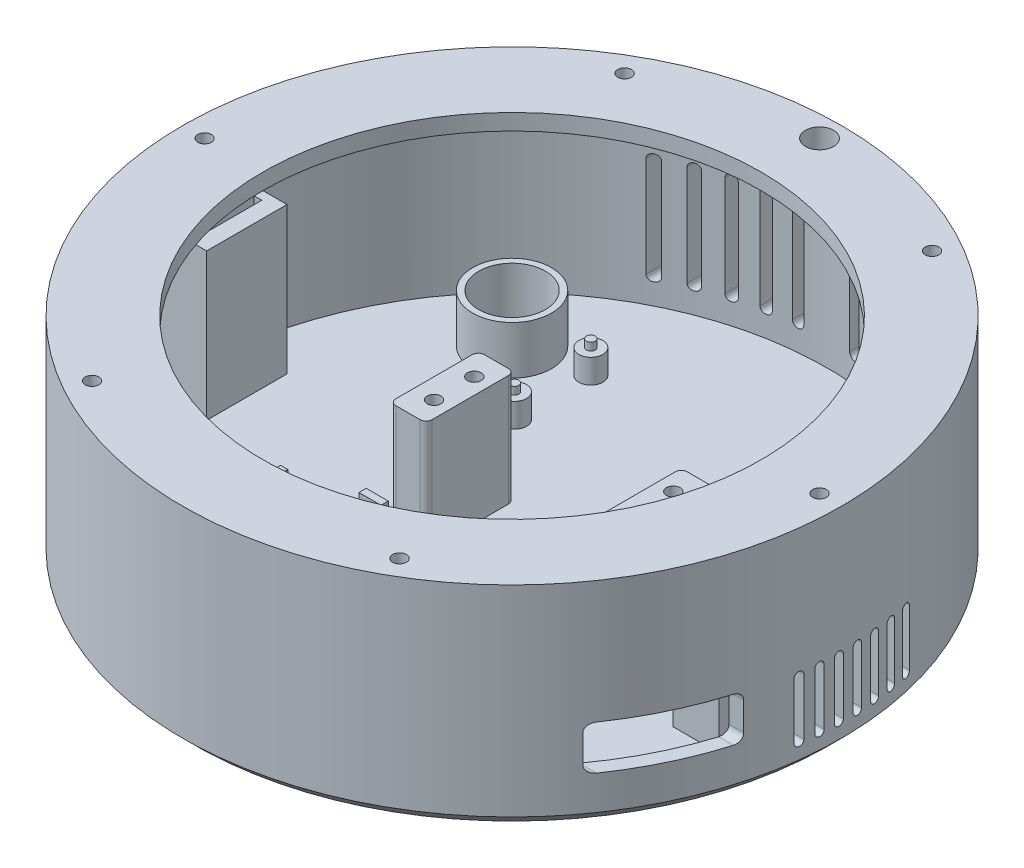
SolidWorks part; units mm, degrees
ref_plane "Front Plane" through (0, 0, 0) normal (0, 0, 1) x (1, 0, 0)
ref_plane "Top Plane" through (0, 0, 0) normal (0, 1, 0) x (1, 0, 0)
ref_plane "Right Plane" through (0, 0, 0) normal (1, 0, 0) x (0, 0, -1)
sketch "Sketch1" plane through (0, 0, 0) normal (0, 0, 1) x (1, 0, 0)
  line L0 (0, -5) -> (0, 80) construction
  line L1 (0, 0) -> (79, 0)
  line L2 (79, 0) -> (82, 3)
  line L3 (82, 3) -> (82, 53)
  line L4 (82, 53) -> (62, 53)
  line L5 (62, 53) -> (62, 49)
  line L6 (62, 49) -> (70.5, 49)
  line L7 (70.5, 49) -> (70.5, 47)
  line L8 (70.5, 47) -> (78.5, 47)
  line L9 (78.5, 47) -> (78.5, 2.5)
  line L10 (78.5, 2.5) -> (0, 2.5)
  line L11 (0, 2.5) -> (0, 0)
revolve "Shell + slew ring" add sketch "Sketch1" angle 360 about L0
sketch "Sketch2" plane through (0, 0, 0) normal (0, 1, 0) x (1, 0, 0)
  line L0 (-17.9, 11) -> (-11.9, 11)
  line L1 (-10.4, 9.5) -> (-10.4, -9.5)
  line L2 (-11.9, -11) -> (-17.9, -11)
  line L3 (-19.4, -9.5) -> (-19.4, 9.5)
  line L4 (32.6, 11) -> (38.6, 11)
  line L5 (40.1, 9.5) -> (40.1, -9.5)
  line L6 (38.6, -11) -> (32.6, -11)
  line L7 (31.1, -9.5) -> (31.1, 9.5)
  arc A0 (-19.4, 9.5) -> (-17.9, 11) centre (-17.9, 9.5) cw
  arc A1 (-11.9, 11) -> (-10.4, 9.5) centre (-11.9, 9.5) cw
  arc A2 (-10.4, -9.5) -> (-11.9, -11) centre (-11.9, -9.5) cw
  arc A3 (-17.9, -11) -> (-19.4, -9.5) centre (-17.9, -9.5) cw
  arc A4 (31.1, 9.5) -> (32.6, 11) centre (32.6, 9.5) cw
  arc A5 (38.6, 11) -> (40.1, 9.5) centre (38.6, 9.5) cw
  arc A6 (40.1, -9.5) -> (38.6, -11) centre (38.6, -9.5) cw
  arc A7 (32.6, -11) -> (31.1, -9.5) centre (32.6, -9.5) cw
extrude "Pan servo pillars" add sketch "Sketch2" along normal blind 27.9 from offset 2.3
sketch "Sketch3" plane through (0, 0, 0) normal (0, 1, 0) x (1, 0, 0)
  circle A0 centre (-14.4, 5) radius 1.7
  circle A1 centre (-14.4, -5) radius 1.7
  circle A2 centre (35.1, 5) radius 1.7
  circle A3 centre (35.1, -5) radius 1.7
extrude "Pillar bolt holes" cut sketch "Sketch3" along normal blind 13.2 from offset 17.2
sketch "Sketch4" plane through (0, 0, 0) normal (0, 1, 0) x (1, 0, 0)
  line L0 (-16.1032, 7.95) -> (-12.6968, 7.95)
  line L1 (-12.6968, 7.95) -> (-10.9936, 5)
  line L2 (-10.9936, 5) -> (-12.6968, 2.05)
  line L3 (-12.6968, 2.05) -> (-16.1032, 2.05)
  line L4 (-16.1032, 2.05) -> (-19.9, 2.05)
  line L5 (-19.9, 2.05) -> (-19.9, 7.95)
  line L6 (-19.9, 7.95) -> (-16.1032, 7.95)
  line L7 (-16.1032, -2.05) -> (-12.6968, -2.05)
  line L8 (-12.6968, -2.05) -> (-10.9936, -5)
  line L9 (-10.9936, -5) -> (-12.6968, -7.95)
  line L10 (-12.6968, -7.95) -> (-16.1032, -7.95)
  line L11 (-16.1032, -7.95) -> (-19.9, -7.95)
  line L12 (-19.9, -7.95) -> (-19.9, -2.05)
  line L13 (-19.9, -2.05) -> (-16.1032, -2.05)
  line L14 (36.8032, 2.05) -> (33.3968, 2.05)
  line L15 (33.3968, 2.05) -> (31.6936, 5)
  line L16 (31.6936, 5) -> (33.3968, 7.95)
  line L17 (33.3968, 7.95) -> (36.8032, 7.95)
  line L18 (36.8032, 7.95) -> (40.6, 7.95)
  line L19 (40.6, 7.95) -> (40.6, 2.05)
  line L20 (40.6, 2.05) -> (36.8032, 2.05)
  line L21 (36.8032, -7.95) -> (33.3968, -7.95)
  line L22 (33.3968, -7.95) -> (31.6936, -5)
  line L23 (31.6936, -5) -> (33.3968, -2.05)
  line L24 (33.3968, -2.05) -> (36.8032, -2.05)
  line L25 (36.8032, -2.05) -> (40.6, -2.05)
  line L26 (40.6, -2.05) -> (40.6, -7.95)
  line L27 (40.6, -7.95) -> (36.8032, -7.95)
extrude "Pillar nut slots" cut sketch "Sketch4" along normal blind 2.7 from offset 21.5
sketch "Sketch5" plane through (0, 0, 0) normal (0, 1, 0) x (1, 0, 0)
  line L0 (30.5, 4.5) -> (40.7, 4.5)
  line L1 (40.7, 4.5) -> (40.7, -4.5)
  line L2 (40.7, -4.5) -> (30.5, -4.5)
  line L3 (30.5, -4.5) -> (30.5, 4.5)
extrude "Servo lead notch" cut sketch "Sketch5" along normal blind 10.7 from offset 2.3
sketch "Sketch6" plane through (0, 0, 0) normal (0, 1, 0) x (1, 0, 0)
  circle A0 centre (-27.9, 47.5) radius 3
  circle A1 centre (-27.9, 28.5) radius 3
  circle A2 centre (27.9, 47.5) radius 3
  circle A3 centre (27.9, 28.5) radius 3
extrude "PCA9685 posts" add sketch "Sketch6" along normal blind 6.2 from offset 2.3
sketch "Sketch7" plane through (0, 0, 0) normal (0, 1, 0) x (1, 0, 0)
  circle A0 centre (-27.9, 47.5) radius 1.1
  circle A1 centre (-27.9, 28.5) radius 1.1
  circle A2 centre (27.9, 47.5) radius 1.1
  circle A3 centre (27.9, 28.5) radius 1.1
extrude "PCA9685 locating pins" add sketch "Sketch7" along normal blind 2.1 from offset 8.3
sketch "Sketch8" plane through (0, 0, 0) normal (0, 1, 0) x (1, 0, 0)
  circle A0 centre (-16.5, -26.5) radius 2.7
  circle A1 centre (-16.5, -43.5) radius 2.7
  circle A2 centre (39.5, -26.5) radius 2.7
  circle A3 centre (39.5, -43.5) radius 2.7
extrude "ESP32 posts" add sketch "Sketch8" along normal blind 10.2 from offset 2.3
sketch "Sketch9" plane through (0, 0, 0) normal (0, 1, 0) x (1, 0, 0)
  line L0 (-13, -19.6) -> (-18.5, -19.6)
  line L1 (-18.5, -19.6) -> (-18.5, -17.8)
  line L2 (-18.5, -17.8) -> (-13, -17.8)
  line L3 (-13, -17.8) -> (-13, -19.6)
  line L4 (-13, -50.4) -> (-18.5, -50.4)
  line L5 (-18.5, -50.4) -> (-18.5, -52.2)
  line L6 (-18.5, -52.2) -> (-13, -52.2)
  line L7 (-13, -52.2) -> (-13, -50.4)
  line L8 (39, -19.6) -> (44.5, -19.6)
  line L9 (44.5, -19.6) -> (44.5, -17.8)
  line L10 (44.5, -17.8) -> (39, -17.8)
  line L11 (39, -17.8) -> (39, -19.6)
  line L12 (39, -50.4) -> (44.5, -50.4)
  line L13 (44.5, -50.4) -> (44.5, -52.2)
  line L14 (44.5, -52.2) -> (39, -52.2)
  line L15 (39, -52.2) -> (39, -50.4)
extrude "ESP32 fences" add sketch "Sketch9" along normal blind 13.2 from offset 2.3
sketch "Sketch10" plane through (0, 0, 0) normal (0, 1, 0) x (1, 0, 0)
  circle A0 centre (-54.5, -27.5) radius 2.7
  circle A1 centre (-54.5, -36) radius 2.7
  circle A2 centre (-39.5, -27.5) radius 2.7
  circle A3 centre (-39.5, -36) radius 2.7
extrude "Amp posts" add sketch "Sketch10" along normal blind 7.7 from offset 2.3
sketch "Sketch11" plane through (0, 0, 0) normal (0, 1, 0) x (1, 0, 0)
  line L0 (-57.4, -26) -> (-59.2, -26)
  line L1 (-59.2, -26) -> (-59.2, -21)
  line L2 (-59.2, -21) -> (-57.4, -21)
  line L3 (-57.4, -21) -> (-57.4, -26)
  line L4 (-57.4, -34) -> (-59.2, -34)
  line L5 (-59.2, -34) -> (-59.2, -39)
  line L6 (-59.2, -39) -> (-57.4, -39)
  line L7 (-57.4, -39) -> (-57.4, -34)
  line L8 (-36.6, -26) -> (-34.8, -26)
  line L9 (-34.8, -26) -> (-34.8, -21)
  line L10 (-34.8, -21) -> (-36.6, -21)
  line L11 (-36.6, -21) -> (-36.6, -26)
  line L12 (-36.6, -34) -> (-34.8, -34)
  line L13 (-34.8, -34) -> (-34.8, -39)
  line L14 (-34.8, -39) -> (-36.6, -39)
  line L15 (-36.6, -39) -> (-36.6, -34)
extrude "Amp fences" add sketch "Sketch11" along normal blind 10.7 from offset 2.3
sketch "Sketch12" plane through (0, 0, 0) normal (0, 1, 0) x (1, 0, 0)
  line L0 (58, -15) -> (69.5, -15)
  line L1 (69.5, -15) -> (69.5, -18)
  line L2 (69.5, -18) -> (58, -18)
  line L3 (58, -18) -> (58, -15)
  line L4 (58, 26) -> (69.5, 26)
  line L5 (69.5, 26) -> (69.5, 23)
  line L6 (69.5, 23) -> (58, 23)
  line L7 (58, 23) -> (58, 26)
extrude "Speaker rails" add sketch "Sketch12" along normal blind 24.2 from offset 2.3
sketch "Sketch13" plane through (0, 0, 0) normal (0, 1, 0) x (1, 0, 0)
  line L0 (60.7, -14.9) -> (66.8, -14.9)
  line L1 (66.8, -14.9) -> (66.8, -16.4)
  line L2 (66.8, -16.4) -> (60.7, -16.4)
  line L3 (60.7, -16.4) -> (60.7, -14.9)
  line L4 (60.7, 24.4) -> (66.8, 24.4)
  line L5 (66.8, 24.4) -> (66.8, 22.9)
  line L6 (66.8, 22.9) -> (60.7, 22.9)
  line L7 (60.7, 22.9) -> (60.7, 24.4)
extrude "Speaker grooves" cut sketch "Sketch13" along normal blind 23.2 from offset 3.5
sketch "Sketch14" plane through (0, 0, 0) normal (0, 1, 0) x (1, 0, 0)
  line L0 (-79.5, 10) -> (-66, 10)
  line L1 (-66, 10) -> (-66, -10)
  line L2 (-66, -10) -> (-79.5, -10)
  line L3 (-79.5, -10) -> (-79.5, 10)
extrude "Mic block" add sketch "Sketch14" along normal blind 36.7 from offset 2.3
sketch "Sketch15" plane through (0, 0, 0) normal (0, 1, 0) x (1, 0, 0)
  line L0 (-71.95, 7.8) -> (-70.05, 7.8)
  line L1 (-70.05, 7.8) -> (-70.05, -7.8)
  line L2 (-70.05, -7.8) -> (-71.95, -7.8)
  line L3 (-71.95, -7.8) -> (-71.95, 7.8)
extrude "Mic slot" cut sketch "Sketch15" along normal blind 17.2 from offset 22
sketch "Sketch16" plane through (0, 0, 0) normal (1, 0, 0) x (0, 0, -1)
  circle A0 centre (0, 30) radius 1.25
extrude "Mic port" cut sketch "Sketch16" along normal blind 19 from offset 90 offset against normal yes
sketch "Sketch17" plane through (0, 0, 0) normal (0, 1, 0) x (1, 0, 0)
  circle A0 centre (-44, 44) radius 9.8
  circle A1 centre (-44, 44) radius 8.3
extrude "Cap clip" add sketch "Sketch17" along normal blind 12.2 from offset 2.3
sketch "Sketch18" plane through (0, 0, 0) normal (1, 0, 0) x (0, 0, -1)
  line L0 (16.9, 7) -> (16.9, 21)
  line L1 (19.1, 21) -> (19.1, 7)
  line L2 (12.2333, 7) -> (12.2333, 21)
  line L3 (14.4333, 21) -> (14.4333, 7)
  line L4 (7.5667, 7) -> (7.5667, 21)
  line L5 (9.7667, 21) -> (9.7667, 7)
  line L6 (2.9, 7) -> (2.9, 21)
  line L7 (5.1, 21) -> (5.1, 7)
  line L8 (-1.7667, 7) -> (-1.7667, 21)
  line L9 (0.4333, 21) -> (0.4333, 7)
  line L10 (-6.4333, 7) -> (-6.4333, 21)
  line L11 (-4.2333, 21) -> (-4.2333, 7)
  line L12 (-11.1, 7) -> (-11.1, 21)
  line L13 (-8.9, 21) -> (-8.9, 7)
  arc A0 (16.9, 21) -> (19.1, 21) centre (18, 21) cw
  arc A1 (19.1, 7) -> (16.9, 7) centre (18, 7) cw
  arc A2 (12.2333, 21) -> (14.4333, 21) centre (13.3333, 21) cw
  arc A3 (14.4333, 7) -> (12.2333, 7) centre (13.3333, 7) cw
  arc A4 (7.5667, 21) -> (9.7667, 21) centre (8.6667, 21) cw
  arc A5 (9.7667, 7) -> (7.5667, 7) centre (8.6667, 7) cw
  arc A6 (2.9, 21) -> (5.1, 21) centre (4, 21) cw
  arc A7 (5.1, 7) -> (2.9, 7) centre (4, 7) cw
  arc A8 (-1.7667, 21) -> (0.4333, 21) centre (-0.6667, 21) cw
  arc A9 (0.4333, 7) -> (-1.7667, 7) centre (-0.6667, 7) cw
  arc A10 (-6.4333, 21) -> (-4.2333, 21) centre (-5.3333, 21) cw
  arc A11 (-4.2333, 7) -> (-6.4333, 7) centre (-5.3333, 7) cw
  arc A12 (-11.1, 21) -> (-8.9, 21) centre (-10, 21) cw
  arc A13 (-8.9, 7) -> (-11.1, 7) centre (-10, 7) cw
extrude "Speaker grille" cut sketch "Sketch18" along normal blind 24 from offset 66
sketch "Sketch19" plane through (0, 0, 0) normal (1, 0, 0) x (0, 0, -1)
  line L0 (-21.5, 13.5) -> (-21.5, 20.5)
  line L1 (-23.5, 22.5) -> (-46.5, 22.5)
  line L2 (-48.5, 20.5) -> (-48.5, 13.5)
  line L3 (-46.5, 11.5) -> (-23.5, 11.5)
  arc A0 (-23.5, 11.5) -> (-21.5, 13.5) centre (-23.5, 13.5) ccw
  arc A1 (-21.5, 20.5) -> (-23.5, 22.5) centre (-23.5, 20.5) ccw
  arc A2 (-46.5, 22.5) -> (-48.5, 20.5) centre (-46.5, 20.5) ccw
  arc A3 (-48.5, 13.5) -> (-46.5, 11.5) centre (-46.5, 13.5) ccw
extrude "USB window" cut sketch "Sketch19" along normal blind 44 from offset 46
sketch "Sketch20" plane through (0, 0, 0) normal (0, 0, 1) x (1, 0, 0)
  line L0 (-36.3, 9) -> (-36.3, 34)
  line L1 (-33.7, 34) -> (-33.7, 9)
  line L2 (-29.3, 9) -> (-29.3, 34)
  line L3 (-26.7, 34) -> (-26.7, 9)
  line L4 (-22.3, 9) -> (-22.3, 34)
  line L5 (-19.7, 34) -> (-19.7, 9)
  line L6 (-15.3, 9) -> (-15.3, 34)
  line L7 (-12.7, 34) -> (-12.7, 9)
  line L8 (-8.3, 9) -> (-8.3, 34)
  line L9 (-5.7, 34) -> (-5.7, 9)
  line L10 (5.7, 9) -> (5.7, 34)
  line L11 (8.3, 34) -> (8.3, 9)
  line L12 (12.7, 9) -> (12.7, 34)
  line L13 (15.3, 34) -> (15.3, 9)
  line L14 (19.7, 9) -> (19.7, 34)
  line L15 (22.3, 34) -> (22.3, 9)
  line L16 (26.7, 9) -> (26.7, 34)
  line L17 (29.3, 34) -> (29.3, 9)
  line L18 (33.7, 9) -> (33.7, 34)
  line L19 (36.3, 34) -> (36.3, 9)
  arc A0 (-36.3, 34) -> (-33.7, 34) centre (-35, 34) cw
  arc A1 (-33.7, 9) -> (-36.3, 9) centre (-35, 9) cw
  arc A2 (-29.3, 34) -> (-26.7, 34) centre (-28, 34) cw
  arc A3 (-26.7, 9) -> (-29.3, 9) centre (-28, 9) cw
  arc A4 (-22.3, 34) -> (-19.7, 34) centre (-21, 34) cw
  arc A5 (-19.7, 9) -> (-22.3, 9) centre (-21, 9) cw
  arc A6 (-15.3, 34) -> (-12.7, 34) centre (-14, 34) cw
  arc A7 (-12.7, 9) -> (-15.3, 9) centre (-14, 9) cw
  arc A8 (-8.3, 34) -> (-5.7, 34) centre (-7, 34) cw
  arc A9 (-5.7, 9) -> (-8.3, 9) centre (-7, 9) cw
  arc A10 (5.7, 34) -> (8.3, 34) centre (7, 34) cw
  arc A11 (8.3, 9) -> (5.7, 9) centre (7, 9) cw
  arc A12 (12.7, 34) -> (15.3, 34) centre (14, 34) cw
  arc A13 (15.3, 9) -> (12.7, 9) centre (14, 9) cw
  arc A14 (19.7, 34) -> (22.3, 34) centre (21, 34) cw
  arc A15 (22.3, 9) -> (19.7, 9) centre (21, 9) cw
  arc A16 (26.7, 34) -> (29.3, 34) centre (28, 34) cw
  arc A17 (29.3, 9) -> (26.7, 9) centre (28, 9) cw
  arc A18 (33.7, 34) -> (36.3, 34) centre (35, 34) cw
  arc A19 (36.3, 9) -> (33.7, 9) centre (35, 9) cw
extrude "Back vents" cut sketch "Sketch20" along normal blind 30 from offset 90 offset against normal yes
sketch "Sketch21" plane through (0, 0, 0) normal (0, 1, 0) x (1, 0, 0)
  circle A0 centre (76.5, 0) radius 1.7
  circle A1 centre (38.25, -66.2509) radius 1.7
  circle A2 centre (-38.25, -66.2509) radius 1.7
  circle A3 centre (-76.5, 0) radius 1.7
  circle A4 centre (-38.25, 66.2509) radius 1.7
  circle A5 centre (38.25, 66.2509) radius 1.7
extrude "Ring bolt holes" cut sketch "Sketch21" along normal blind 6.4 from offset 46.8
sketch "Sketch22" plane through (0, 0, 0) normal (0, 1, 0) x (1, 0, 0)
  line L0 (79.35, -1.6454) -> (76.5, -3.2909)
  line L1 (76.5, -3.2909) -> (73.65, -1.6454)
  line L2 (73.65, -1.6454) -> (73.65, 1.6454)
  line L3 (73.65, 1.6454) -> (76.5, 3.2909)
  line L4 (76.5, 3.2909) -> (79.35, 1.6454)
  line L5 (79.35, 1.6454) -> (79.35, -1.6454)
  line L6 (38.25, -69.5418) -> (35.4, -67.8964)
  line L7 (35.4, -67.8964) -> (35.4, -64.6055)
  line L8 (35.4, -64.6055) -> (38.25, -62.96)
  line L9 (38.25, -62.96) -> (41.1, -64.6055)
  line L10 (41.1, -64.6055) -> (41.1, -67.8964)
  line L11 (41.1, -67.8964) -> (38.25, -69.5418)
  line L12 (-41.1, -67.8964) -> (-41.1, -64.6055)
  line L13 (-41.1, -64.6055) -> (-38.25, -62.96)
  line L14 (-38.25, -62.96) -> (-35.4, -64.6055)
  line L15 (-35.4, -64.6055) -> (-35.4, -67.8964)
  line L16 (-35.4, -67.8964) -> (-38.25, -69.5418)
  line L17 (-38.25, -69.5418) -> (-41.1, -67.8964)
  line L18 (-79.35, 1.6454) -> (-76.5, 3.2909)
  line L19 (-76.5, 3.2909) -> (-73.65, 1.6454)
  line L20 (-73.65, 1.6454) -> (-73.65, -1.6454)
  line L21 (-73.65, -1.6454) -> (-76.5, -3.2909)
  line L22 (-76.5, -3.2909) -> (-79.35, -1.6454)
  line L23 (-79.35, -1.6454) -> (-79.35, 1.6454)
  line L24 (-38.25, 69.5418) -> (-35.4, 67.8964)
  line L25 (-35.4, 67.8964) -> (-35.4, 64.6055)
  line L26 (-35.4, 64.6055) -> (-38.25, 62.96)
  line L27 (-38.25, 62.96) -> (-41.1, 64.6055)
  line L28 (-41.1, 64.6055) -> (-41.1, 67.8964)
  line L29 (-41.1, 67.8964) -> (-38.25, 69.5418)
  line L30 (41.1, 67.8964) -> (41.1, 64.6055)
  line L31 (41.1, 64.6055) -> (38.25, 62.96)
  line L32 (38.25, 62.96) -> (35.4, 64.6055)
  line L33 (35.4, 64.6055) -> (35.4, 67.8964)
  line L34 (35.4, 67.8964) -> (38.25, 69.5418)
  line L35 (38.25, 69.5418) -> (41.1, 67.8964)
extrude "Ring nut pockets" cut sketch "Sketch22" along normal blind 2.9 from offset 46.8
sketch "Sketch23" plane through (0, 0, 0) normal (0, 1, 0) x (1, 0, 0)
  circle A0 centre (0, 76.5) radius 3.5
extrude "MX lead hole" cut sketch "Sketch23" along normal blind 6.4 from offset 46.8
